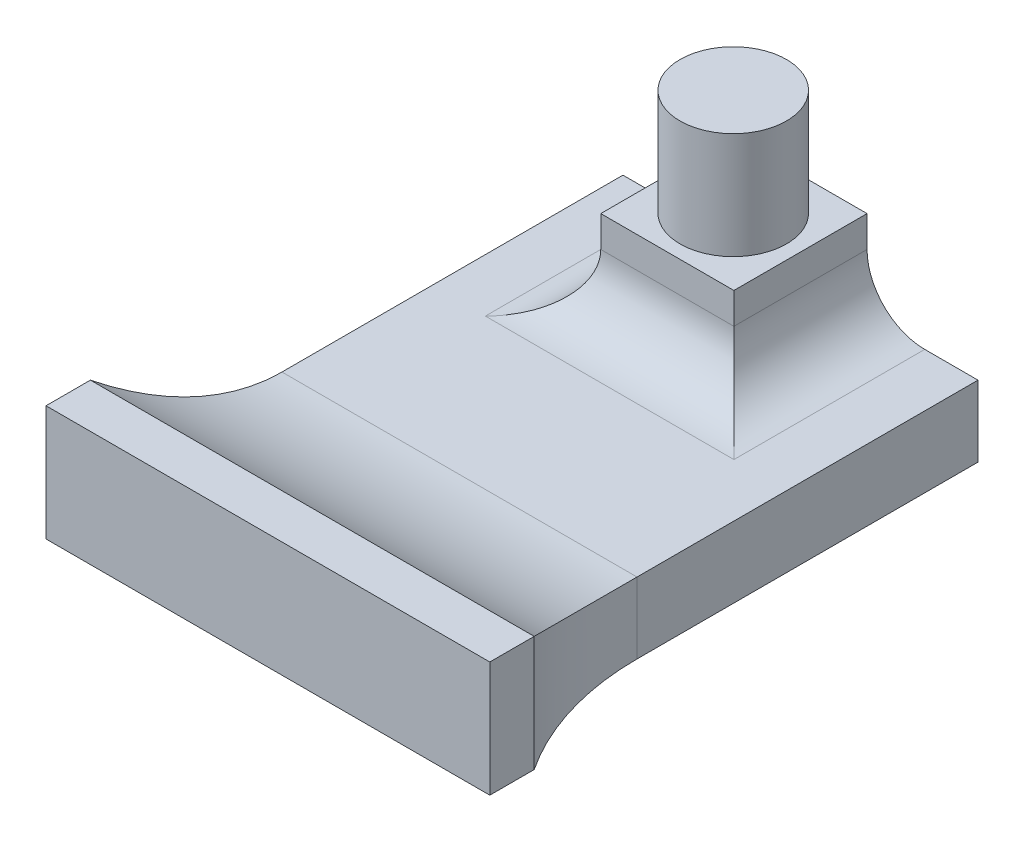
SolidWorks part; units mm, degrees
ref_plane "Front Plane" through (0, 0, 0) normal (0, 0, 1) x (1, 0, 0)
ref_plane "Top Plane" through (0, 0, 0) normal (0, 1, 0) x (1, 0, 0)
ref_plane "Right Plane" through (0, 0, 0) normal (1, 0, 0) x (0, 0, -1)
sketch "Sketch5" plane through (0, 0, 0) normal (0, 0, 1) x (1, 0, 0)
  line L1 (0, 0) -> (-40, 0)
  line L2 (0, 0) -> (0, 10)
  line L3 (0, 10) -> (-40, 10)
  line L4 (-40, 0) -> (-40, 10)
  dimension "D1" = 10
  dimension "3.5" = 40
extrude "Boss-Extrude4" add sketch "Sketch5" along normal blind 60 contours L2 L1 L4 L3
sketch "Sketch11" plane through (0, 10, 0) normal (0, 1, 0) x (1, 0, 0)
  line L1 (-12.5, 0) -> (-27.5, 0)
  line L2 (-12.5, 0) -> (-12.5, -15)
  line L3 (-12.5, -15) -> (-27.5, -15)
  line L4 (-27.5, 0) -> (-27.5, -15)
  line L6 (0, 0) -> (-40, 0) construction
  line L7 (-40, -60) -> (-40, 0) construction
  dimension "D1" = 15
  dimension "D2" = 15
  dimension "D3" = 12.5
  dimension "D4" = 0
extrude "Boss-Extrude6" add sketch "Sketch11" along normal blind 10 contours L2 L1 L4 L3
fillet "Fillet1" radius 6.5 3 edges at (-12.5, 10, 7.5) (-20, 10, 15) (-27.5, 10, 7.5)
sketch "Sketch14" plane through (0, 0, 60) normal (0, 0, 1) x (1, 0, 0)
  line L0 (0, 0) -> (0, 10) construction
  line L1 (-45, 0) -> (5, 0)
  line L2 (-45, 0) -> (-45, 15)
  line L3 (-45, 15) -> (5, 15)
  line L4 (5, 0) -> (5, 15)
  line L5 (0, 0) -> (-40, 0) construction
  dimension "D1" = 50
  dimension "D2" = 15
  dimension "D3" = 5
  dimension "D4" = 0
extrude "Boss-Extrude7" add sketch "Sketch14" against normal blind 5 contours L2 L1 L4 L3
fillet "Fillet2" radius 30 3 edges at (0, 5, 55) (-20, 10, 55) (-40, 5, 55)
sketch "Sketch16" plane through (0, 20, 0) normal (0, 1, 0) x (1, 0, 0)
  line L1 (-45, -60) -> (5, -60) construction
  circle A0 centre (-20.0725, -7.5) radius 6
  dimension "D1" = 12
  dimension "D2" = 52.5
extrude "Boss-Extrude8" add sketch "Sketch16" along normal blind 12
sketch "Sketch17" plane through (0, 0, 0) normal (0, -1, 0) x (-1, 0, 0)
  line L1 (-11.5298, 20.4936) -> (52.5857, 20.4936)
  line L2 (-11.5298, 20.4936) -> (-11.5298, -69.3699)
  line L3 (-11.5298, -69.3699) -> (52.5857, -69.3699)
  line L4 (52.5857, 20.4936) -> (52.5857, -69.3699)
extrude "Cut-Extrude1" cut sketch "Sketch17" against normal blind 2
